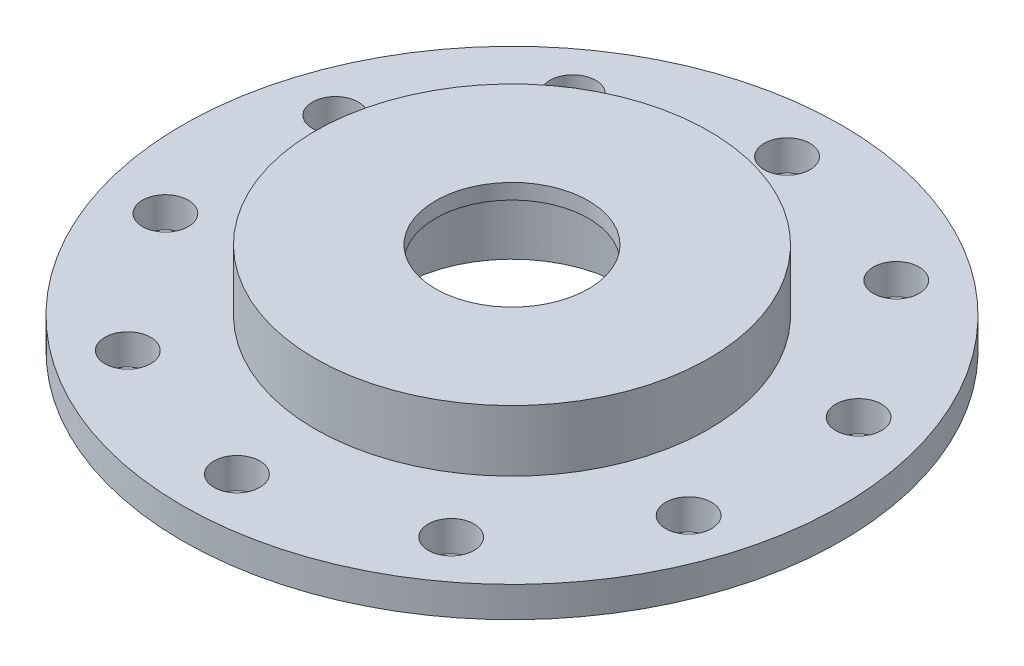
SolidWorks part; units mm, degrees
ref_plane "Front Plane" through (0, 0, 0) normal (0, 0, 1) x (1, 0, 0)
ref_plane "Top Plane" through (0, 0, 0) normal (0, 1, 0) x (1, 0, 0)
ref_plane "Right Plane" through (0, 0, 0) normal (1, 0, 0) x (0, 0, -1)
sketch "Sketch2" plane through (0, 0, 0) normal (0, 1, 0) x (1, 0, 0)
  circle A0 centre (0, 0) radius 107.8268
  circle A1 centre (0, 90) radius 7.5
  circle A2 centre (52.9007, 72.8115) radius 7.5
  circle A3 centre (85.5951, 27.8115) radius 7.5
  circle A4 centre (85.5951, -27.8115) radius 7.5
  circle A5 centre (52.9007, -72.8115) radius 7.5
  circle A6 centre (0, -90) radius 7.5
  circle A7 centre (-52.9007, -72.8115) radius 7.5
  circle A8 centre (-85.5951, -27.8115) radius 7.5
  circle A9 centre (-85.5951, 27.8115) radius 7.5
  circle A10 centre (-52.9007, 72.8115) radius 7.5
  point P26 (0, 0)
  dimension "D1" = 215.6537
  dimension "D3" = 15
  dimension "D2" = 90
  dimension "D4" = 10
extrude "Boss-Extrude1" add sketch "Sketch2" along normal blind 10
sketch "Sketch3" plane through (0, 0, 0) normal (0, -1, 0) x (1, 0, 0)
  circle A0 centre (0, 0) radius 71.687
  circle A1 centre (0, 0) radius 64.4478
  dimension "D1" = 143.374
  dimension "D2" = 128.8957
extrude "Cut-Extrude1" cut sketch "Sketch3" against normal blind 3
sketch "Sketch4" plane through (0, 10, 0) normal (0, 1, 0) x (1, 0, 0)
  line L0 (0, 47.8268) -> (22.9469, 47.8268) construction
  line L1 (0, 64.4478) -> (21.588, 64.4478) construction
  line L3 (-1.5, 57.8268) -> (1.5, 57.8268)
  line L4 (-1.5, 57.8268) -> (-1.5, 52.8268)
  line L5 (-1.5, 52.8268) -> (1.5, 52.8268)
  line L6 (1.5, 57.8268) -> (1.5, 52.8268)
  circle A0 centre (0, 0) radius 64.4478 construction
  circle A1 centre (0, 0) radius 71.687 construction
  circle A2 centre (0, 0) radius 47.8268 construction
  point P13 (0, 52.8268)
  dimension "D1" = 143.374
  dimension "D2" = 128.8957
  dimension "D3" = 95.6537
  dimension "D4" = 5
  dimension "D5" = 5
  dimension "D6" = 3
extrude "Cut-Extrude2" cut sketch "Sketch4" against normal through all
pattern_circular "CirPattern1" count 35 over 360 about axis through (0, 10, 0) along (0, 1, 0) of "Cut-Extrude2"
sketch "Sketch5" plane through (0, 10, 0) normal (0, 1, 0) x (1, 0, 0)
  circle A0 centre (0, 0) radius 47.8268
  dimension "D1" = 95.6537
extrude "Cut-Extrude3" cut sketch "Sketch5" against normal through all
sketch "Sketch6" plane through (0, 10, 0) normal (0, 1, 0) x (1, 0, 0)
  circle A0 centre (0, 0) radius 64.4478
  circle A1 centre (0, 0) radius 47.8268
  dimension "D1" = 128.8957
  dimension "D3" = 95.6537
extrude "Boss-Extrude3" add sketch "Sketch6" along normal blind 10 separate body
sketch "Sketch8" plane through (0, 20, 0) normal (0, 1, 0) x (1, 0, 0)
  line L0 (0, 47.8268) -> (22.9469, 47.8268) construction
  line L1 (0, 64.4478) -> (21.588, 64.4478) construction
  line L3 (-1.5, 57.8268) -> (1.5, 57.8268)
  line L4 (-1.5, 57.8268) -> (-1.5, 52.8268)
  line L5 (-1.5, 52.8268) -> (1.5, 52.8268)
  line L6 (1.5, 57.8268) -> (1.5, 52.8268)
  circle A0 centre (0, 0) radius 64.4478 construction
  circle A1 centre (0, 0) radius 71.687 construction
  circle A2 centre (0, 0) radius 47.8268 construction
  point P13 (0, 52.8268)
  dimension "D1" = 143.374
  dimension "D2" = 128.8957
  dimension "D3" = 95.6537
  dimension "D4" = 5
  dimension "D5" = 5
  dimension "D6" = 3
extrude "Cut-Extrude4" cut sketch "Sketch8" against normal through all
pattern_circular "CirPattern7" count 35 over 360 about axis through (0, 20, 0) along (0, 1, 0) of "Cut-Extrude4"
sketch "Sketch9" plane through (0, 20, 0) normal (0, 1, 0) x (1, 0, 0)
  circle A0 centre (0, 0) radius 64.4478
  circle A1 centre (0, 0) radius 57.8268
  dimension "D1" = 128.8957
  dimension "D2" = 115.6537
extrude "Boss-Extrude4" add sketch "Sketch9" along normal blind 5
sketch "Sketch10" plane through (0, 25, 0) normal (0, 1, 0) x (1, 0, 0)
  circle A0 centre (0, 0) radius 25
  circle A1 centre (0, 0) radius 64.4478
  dimension "D1" = 50
  dimension "D2" = 128.8957
extrude "Boss-Extrude5" add sketch "Sketch10" along normal blind 5
sketch "Sketch11" plane through (0, 10, 0) normal (0, 1, 0) x (1, 0, 0)
  circle A0 centre (0, 0) radius 36.6524
  circle A2 centre (0, 0) radius 47.8268
  dimension "D1" = 73.3048
  dimension "D2" = 95.6537
extrude "Boss-Extrude7" add sketch "Sketch11" along normal blind 10
sketch "Sketch12" plane through (0, 10, 0) normal (0, -1, 0) x (1, 0, 0)
  circle A0 centre (0, 0) radius 36.6524
  circle A1 centre (0, 0) radius 47.8268
  dimension "D1" = 73.3048
  dimension "D2" = 95.6537
extrude "Boss-Extrude8" add sketch "Sketch12" along normal blind 10
equation "\"FuelDia\"= 1.6524"
equation "\"OxDia\"= 1.82924"
equation "\"DistOrifice\"= 10"
equation "\"CantAngle\"= 25deg"
equation "\"RadialDistOrifice\"= 60"
equation "\"Chan_amt\"= 35"
equation "\"Chan_wid\"= 3"
equation "\"Chan_heig\"= 5"
equation "\"bolt_diam\"= 15"
equation "\"oring_inner\"= 128.8956920"
equation "\"oring_outer\"=143.374"
equation "\"oring_thickness\"=3"
equation "\"D3@Sketch2\"=\"bolt_diam\""
equation "\"D1@Sketch3\"=\"oring_outer\""
equation "\"D2@Sketch3\"=\"oring_inner\""
equation "\"D1@Cut-Extrude1\"=\"oring_thickness\""
equation "\"D1@Sketch4\"=\"oring_outer\""
equation "\"D2@Sketch4\"=\"oring_inner\""
equation "\"D3@Sketch4\"=95.6536920"
equation "\"D5@Sketch4\"=\"Chan_heig\""
equation "\"D6@Sketch4\"=\"Chan_wid\""
equation "\"D1@CirPattern1\"=\"Chan_amt\""
equation "\"D1@CirPattern3\"=\"Chan_amt\""
equation "\"D1@CirPattern7\"=\"Chan_amt\""
equation "\"D1@Sketch9\"=\"oring_inner\""
equation "\"D1@Sketch11\"=\"RadialDistOrifice\"+(\"DistOrifice\") + (2*\"FuelDia\")"
equation "\"D1@Sketch12\"=\"RadialDistOrifice\"+(\"DistOrifice\") + (2*\"FuelDia\")"
